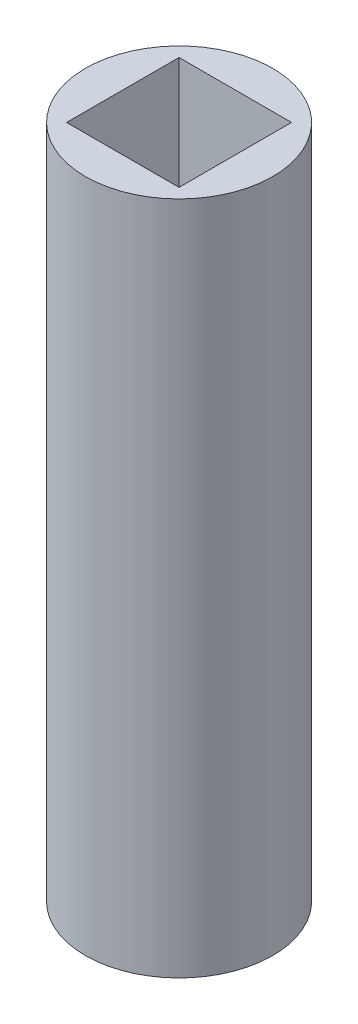
SolidWorks part; units mm, degrees
material "PLA"
ref_plane "Front" through (0, 0, 0) normal (0, 0, 1) x (1, 0, 0)
ref_plane "Top" through (0, 0, 0) normal (0, 1, 0) x (1, 0, 0)
ref_plane "Right" through (0, 0, 0) normal (1, 0, 0) x (0, 0, -1)
sketch "Sketch1" plane through (0, 0, 0) normal (0, 1, 0) x (1, 0, 0)
  circle A0 centre (0, 0) radius 15.875
  dimension "D1" = 31.75
extrude "Boss-Extrude1" add sketch "Sketch1" along normal blind 114.3
sketch "Sketch2" plane through (0, 114.3, 0) normal (0, 1, 0) x (1, 0, 0)
  line L1 (9.525, -9.525) -> (-9.525, -9.525)
  line L2 (9.525, -9.525) -> (9.525, 9.525)
  line L3 (9.525, 9.525) -> (-9.525, 9.525)
  line L4 (-9.525, -9.525) -> (-9.525, 9.525)
  line L5 (9.525, -9.525) -> (-9.525, 9.525) construction
  line L6 (9.525, 9.525) -> (-9.525, -9.525) construction
  point P0 (0, 0)
  dimension "D1" = 19.05
  dimension "D2" = 19.05
extrude "Cut-Extrude1" cut sketch "Sketch2" against normal blind 172.72
